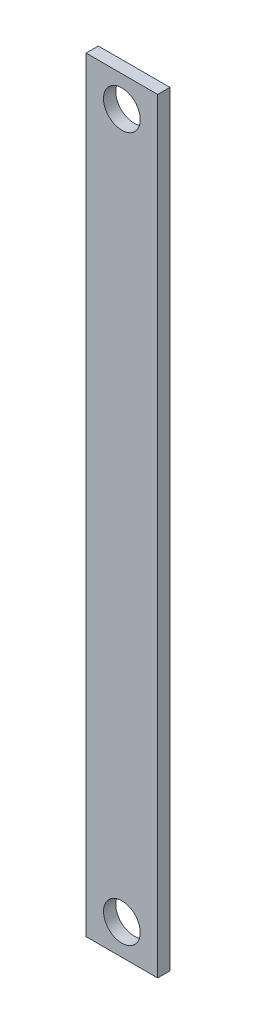
SolidWorks part; units mm, degrees
material "Alloy Steel"
ref_plane "Front Plane" through (0, 0, 0) normal (0, 0, 1) x (1, 0, 0)
ref_plane "Top Plane" through (0, 0, 0) normal (0, 1, 0) x (1, 0, 0)
ref_plane "Right Plane" through (0, 0, 0) normal (1, 0, 0) x (0, 0, -1)
sketch "Sketch1" plane through (0, 0, 0) normal (0, 0, 1) x (1, 0, 0)
  line L1 (-5.85, -62.5) -> (5.85, -62.5)
  line L2 (-5.85, -62.5) -> (-5.85, 62.5)
  line L3 (-5.85, 62.5) -> (5.85, 62.5)
  line L4 (5.85, -62.5) -> (5.85, 62.5)
  line L5 (-5.85, -62.5) -> (5.85, 62.5) construction
  line L6 (-5.85, 62.5) -> (5.85, -62.5) construction
  point P0 (0, 0)
  dimension "D1" = 11.7
  dimension "D2" = 125
extrude "Boss-Extrude1" add sketch "Sketch1" along normal blind 2
sketch "Sketch2" plane through (0, 0, 2) normal (0, 0, 1) x (1, 0, 0)
  line L0 (5.85, 62.5) -> (-5.85, 62.5) construction
  line L1 (-5.85, -62.5) -> (5.85, -62.5) construction
  circle A0 centre (0, 57.5) radius 3
  circle A1 centre (0, -57.5) radius 3
  point P8 (0, 0)
  dimension "D3" = 6
  dimension "D4" = 6
  dimension "D1" = 5
  dimension "D2" = 5
extrude "Cut-Extrude1" cut sketch "Sketch2" against normal through all
equation "\"Largeur\"= 11.7"
equation "\"Longueur\"= 125"
equation "\"Epaisseur\"= 2"
equation "\"D2@Sketch1\"=\"Longueur\""
equation "\"D1@Sketch1\"=\"Largeur\""
equation "\"D1@Boss-Extrude1\"=\"Epaisseur\""
equation "\"LargeurPlaqueEpaisse\"= 10mm"
equation "\"D1@Sketch2\"=\"LargeurPlaqueEpaisse\"/2"
equation "\"D2@Sketch2\"=\"LargeurPlaqueEpaisse\"/2"
equation "\"DiametreTrou\"= 6mm"
equation "\"D3@Sketch2\"=\"DiametreTrou\""
equation "\"D4@Sketch2\"=\"DiametreTrou\""
